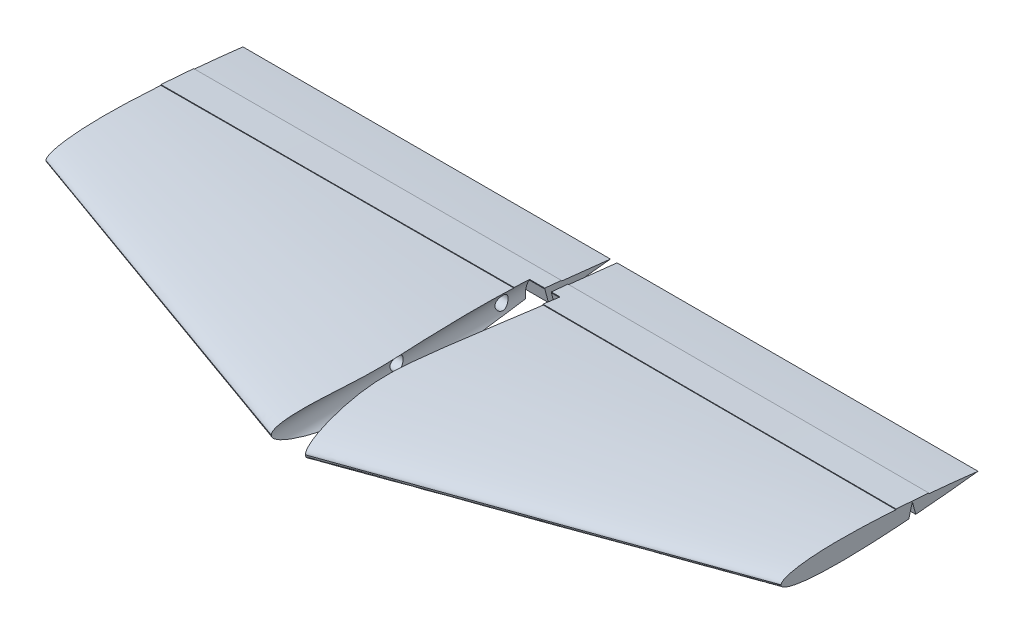
SolidWorks part; units mm, degrees
ref_plane "Front Plane" through (0, 0, 0) normal (0, 0, 1) x (1, 0, 0)
ref_plane "Top Plane" through (0, 0, 0) normal (0, 1, 0) x (1, 0, 0)
ref_plane "Right Plane" through (0, 0, 0) normal (1, 0, 0) x (0, 0, -1)
sketch "Sketch3" plane through (0, 0, 0) normal (1, 0, 0) x (0, 0, -1)
  line L0 (0, 0) -> (-250, 0) construction
  spline S0 degree 4 poles (-250, 0) (-249.9999, 0.1958) (-249.9612, 0.6039) (-249.7596, 1.2633) (-249.1282, 2.2398) (-248.1098, 3.1752) (-246.5761, 4.1828) (-244.1271, 5.3667) (-240.0739, 6.8179) (-232.84, 8.6113) (-221.2945, 10.4497) (-205.8077, 11.8178) (-187.4923, 12.5325) (-167.6157, 12.5624) (-147.9613, 12.1042) (-127.9831, 11.2209) (-108.5655, 10.1073) (-88.2725, 8.6479) (-69.4578, 7.1641) (-48.2492, 5.205) (-31.0441, 3.5474) (-5.6278, 0.7144) (5.3818, -0.6305) (19.3913, -2.4508) (24.9342, -3.2323) knots 0 0 0 0 0 0.002791 0.005883 0.009735 0.016522 0.022438 0.032158 0.048634 0.078249 0.129037 0.199997 0.270957 0.341918 0.412878 0.483838 0.554798 0.625759 0.696719 0.767679 0.83864 0.9096 1 1 1 1 1 construction
  spline S1 degree 4 poles (-250, 0) (-249.9999, 0.1958) (-249.9612, 0.6039) (-249.7596, 1.2633) (-249.1282, 2.2398) (-248.1098, 3.1752) (-246.5761, 4.1828) (-244.1271, 5.3667) (-240.0739, 6.8179) (-232.84, 8.6113) (-221.2945, 10.4497) (-205.8077, 11.8178) (-187.4923, 12.5325) (-167.6157, 12.5624) (-147.9613, 12.1042) (-127.9831, 11.2209) (-108.5655, 10.1073) (-88.2725, 8.6479) (-69.4578, 7.1641) (-48.2492, 5.205) (-31.0441, 3.5474) (-13.2038, 1.5588) (-4.4672, 0.5411) (0, 0) knots 0 0 0 0 0 0.002791 0.005883 0.009735 0.016522 0.022438 0.032158 0.048634 0.078249 0.129037 0.199997 0.270957 0.341918 0.412878 0.483838 0.554798 0.625759 0.696719 0.767679 0.83864 0.9096 0.9096 0.9096 0.9096 0.9096
  spline S2 degree 4 poles (-250, 0) (-249.9999, -0.1958) (-249.9612, -0.6039) (-249.7596, -1.2633) (-249.1282, -2.2398) (-248.1098, -3.1752) (-246.5761, -4.1828) (-244.1271, -5.3667) (-240.0739, -6.8179) (-232.84, -8.6113) (-221.2945, -10.4497) (-205.8077, -11.8178) (-187.4923, -12.5325) (-167.6157, -12.5624) (-147.9613, -12.1042) (-127.9831, -11.2209) (-108.5655, -10.1073) (-88.2725, -8.6479) (-69.4578, -7.1641) (-48.2492, -5.205) (-31.0441, -3.5474) (-13.2038, -1.5588) (-4.4672, -0.5411) (0, 0) knots 0 0 0 0 0 0.002791 0.005883 0.009735 0.016522 0.022438 0.032158 0.048634 0.078249 0.129037 0.199997 0.270957 0.341918 0.412878 0.483838 0.554798 0.625759 0.696719 0.767679 0.83864 0.9096 0.9096 0.9096 0.9096 0.9096
  dimension "D1" = 250
ref_plane "Plane1" through (280, 0, 0) normal (1, 0, 0) x (0, 0, -1)
sketch "Sketch4" plane through (280, 0, 0) normal (1, 0, 0) x (0, 0, -1)
  line L0 (0, 0) -> (-150, 0) construction
  spline S0 degree 4 poles (-150, 0) (-149.9999, 0.1175) (-149.9767, 0.3624) (-149.8557, 0.758) (-149.4769, 1.3439) (-148.8659, 1.9051) (-147.9457, 2.5097) (-146.4763, 3.22) (-144.0443, 4.0908) (-139.704, 5.1668) (-132.7767, 6.2698) (-123.4846, 7.0907) (-112.4954, 7.5195) (-100.5694, 7.5374) (-88.7768, 7.2625) (-76.7899, 6.7325) (-65.1393, 6.0644) (-52.9635, 5.1887) (-41.6747, 4.2985) (-28.9495, 3.123) (-18.6265, 2.1284) (-3.3767, 0.4286) (3.2291, -0.3783) (11.6348, -1.4705) (14.9605, -1.9394) knots 0 0 0 0 0 0.002791 0.005883 0.009735 0.016522 0.022438 0.032158 0.048634 0.078249 0.129037 0.199997 0.270957 0.341918 0.412878 0.483838 0.554798 0.625759 0.696719 0.767679 0.83864 0.9096 1 1 1 1 1 construction
  spline S1 degree 4 poles (-150, 0) (-149.9999, 0.1175) (-149.9767, 0.3624) (-149.8557, 0.758) (-149.4769, 1.3439) (-148.8659, 1.9051) (-147.9457, 2.5097) (-146.4763, 3.22) (-144.0443, 4.0908) (-139.704, 5.1668) (-132.7767, 6.2698) (-123.4846, 7.0907) (-112.4954, 7.5195) (-100.5694, 7.5374) (-88.7768, 7.2625) (-76.7899, 6.7325) (-65.1393, 6.0644) (-52.9635, 5.1887) (-41.6747, 4.2985) (-28.9495, 3.123) (-18.6265, 2.1284) (-7.9223, 0.9353) (-2.6803, 0.3247) (0, 0) knots 0 0 0 0 0 0.002791 0.005883 0.009735 0.016522 0.022438 0.032158 0.048634 0.078249 0.129037 0.199997 0.270957 0.341918 0.412878 0.483838 0.554798 0.625759 0.696719 0.767679 0.83864 0.9096 0.9096 0.9096 0.9096 0.9096
  spline S2 degree 4 poles (-150, 0) (-149.9999, -0.1175) (-149.9767, -0.3624) (-149.8557, -0.758) (-149.4769, -1.3439) (-148.8659, -1.9051) (-147.9457, -2.5097) (-146.4763, -3.22) (-144.0443, -4.0908) (-139.704, -5.1668) (-132.7767, -6.2698) (-123.4846, -7.0907) (-112.4954, -7.5195) (-100.5694, -7.5374) (-88.7768, -7.2625) (-76.7899, -6.7325) (-65.1393, -6.0644) (-52.9635, -5.1887) (-41.6747, -4.2985) (-28.9495, -3.123) (-18.6265, -2.1284) (-7.9223, -0.9353) (-2.6803, -0.3247) (0, 0) knots 0 0 0 0 0 0.002791 0.005883 0.009735 0.016522 0.022438 0.032158 0.048634 0.078249 0.129037 0.199997 0.270957 0.341918 0.412878 0.483838 0.554798 0.625759 0.696719 0.767679 0.83864 0.9096 0.9096 0.9096 0.9096 0.9096
loft "Loft1" add profiles "Sketch3", "Sketch4" connector at (0, 0, 0) connector at (280, 0, 0)
sketch "Sketch6" plane through (0, 0, 0) normal (-1, 0, 0) x (0, 0, 1)
  line L0 (0, 0) -> (249.9998, 0) construction
  line L1 (50, 0) -> (50, 5.2226) construction
  line L2 (50, 5.2226) -> (52.9065, -5.6245)
  line L3 (50, 5.2226) -> (47.2363, -5.0918)
  line L4 (52.9065, -5.6245) -> (53.3084, -7.1245)
  line L5 (53.3084, -7.1245) -> (46.6916, -7.1245)
  line L6 (46.6916, -7.1245) -> (47.2363, -5.0918)
  spline S1 degree 3 poles (249.9998, 0) (249.9998, -0.3303) (249.8759, -0.9899) (249.3864, -1.8624) (248.7238, -2.6034) (247.962, -3.2402) (247.1416, -3.797) (246.2828, -4.2923) (245.3979, -4.7388) (244.193, -5.2813) (242.6531, -5.88) (240.7719, -6.5042) (238.8684, -7.0564) (236.9492, -7.551) (235.0183, -7.9974) (233.0787, -8.4038) (231.1322, -8.7761) (229.1802, -9.1183) (227.2237, -9.4331) (225.2633, -9.7232) (223.2997, -9.9908) (220.6781, -10.3206) (217.3955, -10.6866) (213.4499, -11.0625) (209.4994, -11.3825) (205.5452, -11.6532) (201.5883, -11.8796) (197.6292, -12.0662) (193.6687, -12.2161) (188.3864, -12.3703) (181.7816, -12.4844) (173.8547, -12.5144) (165.9281, -12.4534) (158.0025, -12.3124) (150.0786, -12.0979) (142.1568, -11.8164) (134.2373, -11.4769) (126.32, -11.0887) (118.4051, -10.6559) (110.4927, -10.178) (102.5832, -9.6561) (94.6761, -9.0972) (86.7712, -8.5097) (78.8683, -7.8944) (70.9683, -7.2438) (63.0715, -6.5557) (55.1773, -5.8381) (47.285, -5.1002) (39.3948, -4.3397) (31.5085, -3.54) (23.6262, -2.7007) (13.1211, -1.5408) (5.2462, -0.6354) (0, 0) knots 0.499997 0.499997 0.499997 0.499997 0.50195 0.503903 0.505856 0.507809 0.509763 0.511716 0.513669 0.515622 0.519528 0.523435 0.527341 0.531247 0.535153 0.53906 0.542966 0.546872 0.550778 0.554685 0.558591 0.562497 0.57031 0.578122 0.585935 0.593748 0.60156 0.609373 0.617185 0.624998 0.640623 0.656248 0.671873 0.687498 0.703123 0.718748 0.734373 0.749998 0.765624 0.781249 0.796874 0.812499 0.828124 0.843749 0.859374 0.874999 0.890624 0.906249 0.921875 0.9375 0.953125 0.96875 1 1 1 1 construction
  dimension "D1" = 50
  dimension "D2" = 15
  dimension "D3" = 15
  dimension "D4" = 1.5
sketch "Sketch7" plane through (280, 0, 0) normal (1, 0, 0) x (0, 0, -1)
  line L0 (-149.9999, 0) -> (0, 0) construction
  line L1 (-50, 0) -> (-50, 4.8685) construction
  line L2 (-50, 4.8685) -> (-47.425, -4.7416)
  line L3 (-50, 4.8685) -> (-52.6846, -5.1507)
  line L4 (-52.6846, -5.1507) -> (-53.0866, -6.6507)
  line L5 (-53.0866, -6.6507) -> (-46.9134, -6.6507)
  line L6 (-46.9134, -6.6507) -> (-47.425, -4.7416)
  spline S1 degree 2 poles (-149.9999, 0) (-149.9999, -1.0092) (-148.7713, -1.9362) (-147.9824, -2.5314) (-146.6951, -3.0843) (-144.8841, -3.862) (-142.1683, -4.5258) (-138.2655, -5.4797) (-132.7998, -6.141) (-128.4814, -6.6636) (-123.3268, -6.9875) (-118.8418, -7.2693) (-113.824, -7.3959) (-105.2058, -7.6134) (-94.8016, -7.3801) (-86.1557, -7.1862) (-75.7922, -6.6487) (-71.0007, -6.4001) (-66.2959, -6.1026) (-61.9956, -5.8307) (-56.8059, -5.4552) (-51.7767, -5.0913) (-47.3212, -4.7333) (-42.7854, -4.3688) (-37.8431, -3.9303) (-33.2978, -3.527) (-28.3712, -3.0577) (-23.1272, -2.5583) (-18.9054, -2.1204) (-14.7262, -1.687) (-9.4487, -1.0957) (-4.0863, -0.4949) (0, 0) knots 0 0 0 0.015625 0.015625 0.03125 0.03125 0.0625 0.0625 0.125 0.125 0.1875 0.1875 0.25 0.25 0.375 0.375 0.5 0.5 0.5625 0.5625 0.625 0.625 0.6875 0.6875 0.75 0.75 0.8125 0.8125 0.875 0.875 0.9375 0.9375 1 1 1 construction
  dimension "D1" = 50
  dimension "D2" = 15
  dimension "D3" = 15
  dimension "D4" = 1.5
loft "Cut-Loft1" cut profiles "Sketch6", "Sketch7" connector at (0, -5.0918, 47.2363) connector at (280, -4.7416, 47.425)
sketch "Sketch8" plane through (0, 0, 0) normal (-1, 0, 0) x (0, 0, 1)
  line L0 (0, 0) -> (249.9998, 0) construction
  circle A0 centre (70, 0) radius 5
  point P4 (70, 0)
  dimension "D1" = 70
  dimension "D2" = 10
sketch "Sketch15" plane through (280, 0, 0) normal (1, 0, 0) x (0, 0, -1)
  line L0 (-62.5, 5.8541) -> (-37.5, 3.8998)
  line L1 (-37.5, 3.8998) -> (-37.4609, 4.3998)
  line L2 (-37.4609, 4.3998) -> (-62.4609, 6.3541)
  line L3 (-62.4609, 6.3541) -> (-62.5, 5.8541)
  spline S0 degree 2 poles (0, 0) (-4.0859, 0.4949) (-9.4487, 1.0957) (-14.7252, 1.6868) (-18.9054, 2.1204) (-23.1261, 2.5582) (-28.3712, 3.0577) (-33.2967, 3.5269) (-37.8431, 3.9303) (-42.7843, 4.3687) (-47.3212, 4.7333) (-51.7756, 5.0912) (-56.8059, 5.4552) (-61.9946, 5.8306) (-66.2959, 6.1026) (-70.9996, 6.4001) (-75.7922, 6.6487) (-86.1547, 7.1862) (-94.8016, 7.3801) (-105.2047, 7.6134) (-113.824, 7.3959) (-118.8407, 7.2694) (-123.3268, 6.9875) (-128.4803, 6.6637) (-132.7998, 6.141) (-138.2644, 5.4798) (-142.1683, 4.5258) (-144.883, 3.8624) (-146.6951, 3.0843) (-147.9815, 2.5319) (-148.7713, 1.9362) (-149.9999, 1.0095) (-149.9999, 0) knots 0 0 0 0.0625 0.0625 0.125 0.125 0.1875 0.1875 0.25 0.25 0.3125 0.3125 0.375 0.375 0.4375 0.4375 0.5 0.5 0.625 0.625 0.75 0.75 0.8125 0.8125 0.875 0.875 0.9375 0.9375 0.96875 0.96875 0.984375 0.984375 1 1 1 construction
  dimension "D1" = 0.5
  dimension "D2" = 25
  dimension "D3" = 12.5
sketch "Sketch16" plane through (0, 0, 0) normal (-1, 0, 0) x (0, 0, 1)
  line L0 (37.4356, 4.1381) -> (62.4356, 6.494)
  line L1 (37.4356, 4.1381) -> (37.3884, 4.6381)
  line L2 (62.4356, 6.494) -> (62.3884, 6.994)
  line L3 (37.3884, 4.6381) -> (62.3884, 6.994)
  spline S0 degree 3 poles (0, 0) (5.2462, 0.6354) (13.1211, 1.5408) (23.6262, 2.7007) (31.5085, 3.54) (39.3948, 4.3397) (47.285, 5.1002) (55.1773, 5.8381) (63.0715, 6.5557) (70.9683, 7.2438) (78.8683, 7.8944) (86.7712, 8.5097) (94.6761, 9.0972) (102.5832, 9.6561) (110.4927, 10.178) (118.4051, 10.6559) (126.32, 11.0887) (134.2373, 11.4769) (142.1568, 11.8164) (150.0786, 12.0979) (158.0025, 12.3124) (165.9281, 12.4534) (173.8547, 12.5144) (181.7816, 12.4844) (188.3864, 12.3703) (193.6687, 12.2161) (197.6292, 12.0662) (201.5883, 11.8796) (205.5452, 11.6532) (209.4994, 11.3825) (213.4499, 11.0625) (217.3955, 10.6866) (220.6781, 10.3206) (223.2997, 9.9908) (225.2633, 9.7232) (227.2237, 9.4331) (229.1802, 9.1183) (231.1322, 8.7761) (233.0787, 8.4038) (235.0183, 7.9974) (236.9492, 7.551) (238.8684, 7.0564) (240.7719, 6.5042) (242.6531, 5.88) (244.193, 5.2813) (245.3979, 4.7388) (246.2828, 4.2923) (247.1416, 3.797) (247.962, 3.2402) (248.7238, 2.6034) (249.3864, 1.8624) (249.8759, 0.9899) (249.9998, 0.3303) (249.9998, 0) knots 0 0 0 0 0.03125 0.046875 0.0625 0.078125 0.093749 0.109374 0.124999 0.140624 0.156249 0.171874 0.187499 0.203124 0.218749 0.234374 0.249998 0.265623 0.281248 0.296873 0.312498 0.328123 0.343748 0.359373 0.374998 0.38281 0.390623 0.398435 0.406248 0.41406 0.421872 0.429685 0.437497 0.441404 0.44531 0.449216 0.453122 0.457028 0.460935 0.464841 0.468747 0.472653 0.47656 0.480466 0.484372 0.486325 0.488278 0.490231 0.492184 0.494138 0.496091 0.498044 0.499997 0.499997 0.499997 0.499997 construction
  dimension "D1" = 0.5
  dimension "D2" = 25
  dimension "D3" = 12.5
loft "Loft2" add profiles "Sketch15", "Sketch16" connector at (280, 4.3998, 37.4609) connector at (0, 4.6381, 37.3884)
ref_plane "Plane4" through (0, 0, 50) normal (0, 0, 1) x (1, 0, 0)
sketch "Sketch14" plane through (0, 0, 0) normal (0, 1, 0) x (1, 0, 0)
  line L0 (0, -14.3) -> (0, 14.3) construction
  line L1 (-5, 0) -> (5, 0)
  line L2 (-5, 0) -> (-5, -75)
  line L3 (-5, -75) -> (5, -75)
  line L4 (5, 0) -> (5, -75)
  line L5 (-14.3, 0) -> (14.3, 0) construction
  dimension "10" = 10
  dimension "D2" = 5
  dimension "D3" = 75
extrude "Cut-Extrude6" cut sketch "Sketch14" against normal through all and the other way through all
sketch "Sketch17" plane through (0, 0, 0) normal (0, 1, 0) x (1, 0, 0)
  line L0 (0, -14.3) -> (0, 14.3) construction
  line L1 (40, -80) -> (84, -80)
  line L2 (40, -80) -> (40, -124)
  line L3 (40, -124) -> (84, -124)
  line L4 (84, -80) -> (84, -124)
  line L5 (-40, -80) -> (-84, -80)
  line L6 (-40, -80) -> (-40, -124)
  line L7 (-40, -124) -> (-84, -124)
  line L8 (-84, -80) -> (-84, -124)
  line L9 (-14.3, 0) -> (14.3, 0) construction
  dimension "D1" = 44
  dimension "D2" = 44
  dimension "D3" = 44
  dimension "D4" = 44
  dimension "D5" = 40
  dimension "D6" = 80
  dimension "D7" = 80
  dimension "D8" = 40
extrude "Cut-Extrude7" cut sketch "Sketch17" against normal through all and the other way blind 5
extrude "Cut-Extrude10" cut sketch "Sketch8" against normal blind 100
sketch "Sketch18" plane through (0, 0, 0) normal (1, 0, 0) x (0, 0, -1)
  line L0 (0, 0) -> (-250, 0) construction
  circle A0 centre (-150, 0) radius 5
  dimension "D2" = 10
  dimension "D1" = 250
  dimension "D3" = 100
extrude "Cut-Extrude11" cut sketch "Sketch18" along normal blind 150 contours A0
sketch "Sketch19" plane through (0, 0, 0) normal (1, 0, 0) x (0, 0, -1)
  circle A0 centre (-70, 0) radius 4
  circle A1 centre (-150, 0) radius 4
  circle A2 centre (-150, 0) radius 5
  circle A3 centre (-70, 0) radius 4.95
  dimension "D1" = 9.9
  dimension "D2" = 10
  dimension "D3" = 8
  dimension "D4" = 8
mirror "Mirror7" about plane through (0, 0, 0) normal (1, 0, 0) of "Cut-Extrude7", "Cut-Extrude11", "Cut-Extrude10", "Cut-Loft1", "Loft2", "Loft1"
sketch "Sketch13" plane through (0, 0, 50) normal (0, 0, 1) x (1, 0, 0)
  circle A0 centre (0, 0) radius 13
  dimension "D1" = 26
extrude "Cut-Extrude5" cut sketch "Sketch13" along normal through all
